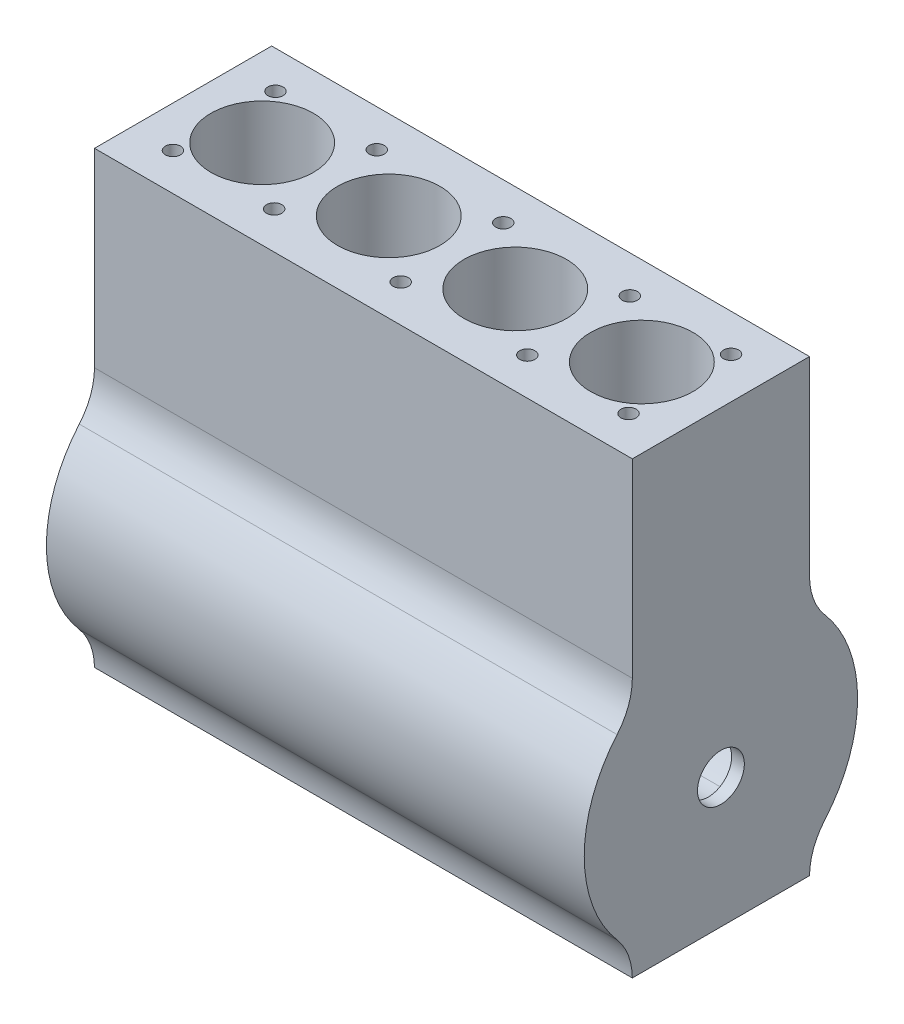
SolidWorks part; units mm, degrees
ref_plane "Front Plane" through (0, 0, 0) normal (0, 0, 1) x (1, 0, 0)
ref_plane "Top Plane" through (0, 0, 0) normal (0, 1, 0) x (1, 0, 0)
ref_plane "Right Plane" through (0, 0, 0) normal (1, 0, 0) x (0, 0, -1)
sketch "Sketch1" plane through (0, 0, 0) normal (0, 1, 0) x (1, 0, 0)
  line L0 (0, 0) -> (62.5, 0)
  line L1 (62.5, 0) -> (162.5, 0)
  line L2 (162.5, 0) -> (262.5, 0)
  line L3 (262.5, 0) -> (362.5, 0)
  line L4 (362.5, 0) -> (425, 0)
  line L5 (0, 0) -> (0, 70) construction
  line L6 (425, 0) -> (425, -70) construction
  line L8 (0, 70) -> (425, 70)
  line L9 (0, 70) -> (0, -70)
  line L10 (0, -70) -> (425, -70)
  line L11 (425, 70) -> (425, -70)
  circle A0 centre (62.5, 0) radius 40.5015
  circle A1 centre (162.5, 0) radius 40.5015
  circle A2 centre (262.5, 0) radius 40.5015
  circle A3 centre (362.5, 0) radius 40.5015
  dimension "D6" = 81.003
  dimension "D7" = 81.003
  dimension "D8" = 81.003
  dimension "D9" = 81.003
  dimension "D1" = 62.5
  dimension "D2" = 100
  dimension "D3" = 100
  dimension "D4" = 100
  dimension "D5" = 62.5
  dimension "D10" = 70
  dimension "D11" = 70
  dimension "D12" = 425
extrude "Boss-Extrude1" add sketch "Sketch1" along normal blind 350 contours A3 L3 A2 L2 A1 L1 A0 L0 L9 L10 L11 L4 | A3 L4 L11 L8 L9 L0 A0 L1 A1 L2 A2 L3 region at (212.5, 0, -44.4413) region at (212.5, 0, 44.4413)
sketch "Sketch2" plane through (0, 0, 0) normal (0, -1, 0) x (1, 0, 0)
  line L14 (415, -60) -> (415, 60)
  line L15 (10, -60) -> (415, -60)
  line L16 (10, 60) -> (10, -60)
  line L17 (415, 60) -> (10, 60)
  line L18 (415, -60) -> (415, 60)
  line L19 (10, -60) -> (415, -60)
  line L20 (10, 60) -> (10, -60)
  line L21 (415, 60) -> (10, 60)
  dimension "D1" = 10
extrude "Cut-Extrude1" cut sketch "Sketch2" against normal blind 250
sketch "Sketch3" plane through (0, 0, 0) normal (-1, 0, 0) x (0, 0, 1)
  circle A0 centre (0, 102.3197) radius 18.5
  dimension "D1" = 37
extrude "Cut-Extrude2" cut sketch "Sketch3" against normal blind 425
sketch "Sketch5" plane through (0, 0, 0) normal (-1, 0, 0) x (0, 0, 1)
  line L0 (-70, 184.5633) -> (-70, 20.0762)
  line L1 (-70, 350) -> (-70, 0) construction
  line L3 (70, 184.5633) -> (70, 20.0762)
  line L5 (70, 350) -> (70, 0) construction
  circle A0 centre (0, 102.3197) radius 108
  dimension "D1" = 216
extrude "Boss-Extrude4" add sketch "Sketch5" against normal blind 425 contours L1 A0 | A0 region at (0, 102.3197, -85.4554) region at (0, 102.3197, 85.4554)
ref_plane "Plane2" through (10, 0, 0) normal (-1, 0, 0) x (0, 0, 1)
sketch "Sketch7" plane through (10, 0, 0) normal (-1, 0, 0) x (0, 0, 1)
  circle A0 centre (0, 102.3197) radius 99
  dimension "D1" = 198
extrude "Cut-Extrude4" cut sketch "Sketch7" against normal blind 405
fillet "Fillet1" radius 20 4 edges at (212.5, 23.5733, -60) (212.5, 23.5733, 60) (212.5, 181.0661, -60) (212.5, 181.0661, 60)
fillet "Fillet2" radius 50 4 edges at (212.5, 20.0762, -70) (212.5, 20.0762, 70) (212.5, 184.5633, 70) (212.5, 184.5633, -70)
sketch "Sketch8" plane through (0, 350, 0) normal (0, 1, 0) x (1, 0, 0)
  line L0 (62.5, 40.5015) -> (362.5, 40.5015) construction
  line L1 (62.5, -40.5015) -> (362.5, -40.5015) construction
  line L2 (62.5, 0) -> (162.5, 0) construction
  line L3 (162.5, 0) -> (262.5, 0) construction
  line L4 (262.5, 0) -> (362.5, 0) construction
  line L5 (112.5, -40.5015) -> (112.5, 40.5015) construction
  line L6 (212.5, -40.5015) -> (212.5, 40.5015) construction
  line L7 (312.5, -40.5015) -> (312.5, 40.5015) construction
  line L8 (62.5, 40.5015) -> (12.5, 40.5015) construction
  line L9 (62.5, -40.5015) -> (12.5, -40.5015) construction
  line L10 (362.5, 40.5015) -> (412.5, 40.5015) construction
  line L11 (362.5, -40.5015) -> (412.5, -40.5015) construction
  line L12 (425, -82.0253) -> (425, -70) construction
  line L13 (0, 70) -> (425, 70)
  line L14 (0, 70) -> (0, -70)
  line L15 (0, -70) -> (425, -70)
  line L16 (425, 70) -> (425, -70)
  line L17 (0, -70) -> (425, -70) construction
  circle A0 centre (62.5, 0) radius 40.5015 construction
  circle A1 centre (362.5, 0) radius 40.5015 construction
  circle A2 centre (112.5, 40.5015) radius 6
  circle A3 centre (112.5, -40.5015) radius 6
  circle A4 centre (212.5, -40.5015) radius 6
  circle A5 centre (212.5, 40.5015) radius 6
  circle A6 centre (312.5, -40.5015) radius 6
  circle A7 centre (312.5, 40.5015) radius 6
  circle A8 centre (12.5, 40.5015) radius 6
  circle A9 centre (12.5, -40.5015) radius 6
  circle A10 centre (412.5, -40.5015) radius 6
  circle A11 centre (412.5, 40.5015) radius 6
  circle A12 centre (62.5, 0) radius 40.5015
  circle A13 centre (162.5, 0) radius 40.5015
  circle A14 centre (262.5, 0) radius 40.5015
  circle A15 centre (362.5, 0) radius 40.5015
  point P17 (112.5, 0)
  point P20 (212.5, 0)
  point P23 (312.5, 0)
  dimension "D4" = 12
  dimension "D5" = 12
  dimension "D6" = 12
  dimension "D7" = 12
  dimension "D8" = 12
  dimension "D9" = 12
  dimension "D14" = 12
  dimension "D15" = 12
  dimension "D16" = 12
  dimension "D17" = 12
  dimension "D1" = 100
  dimension "D2" = 100
  dimension "D3" = 100
  dimension "D10" = 50
  dimension "D11" = 50
  dimension "D12" = 50
  dimension "D13" = 50
extrude "Boss-Extrude5" add sketch "Sketch8" along normal blind 5.28
sketch "Sketch9" plane through (0, 355.28, 0) normal (0, 1, 0) x (1, 0, 0)
  line L0 (12.5, 40.5015) -> (0, 40.5015)
  line L1 (12.5, -40.5015) -> (0, -40.5015)
  line L2 (412.5, -40.5015) -> (425, -40.5015)
  line L3 (412.5, 40.5015) -> (425, 40.5015)
  line L4 (0, 70) -> (0, -70)
  line L5 (0, -70) -> (425, -70)
  line L6 (425, -70) -> (425, 70)
  line L7 (425, 70) -> (0, 70)
  line L8 (0, 70) -> (0, -70)
  line L9 (0, -70) -> (425, -70)
  line L10 (425, -70) -> (425, 70)
  line L11 (425, 70) -> (0, 70)
  line L12 (0, 40.5015) -> (32.5, 40.5015)
  line L13 (0, -40.5015) -> (32.5, -40.5015)
  line L14 (425, -40.5015) -> (392.5, -40.5015)
  line L15 (425, 40.5015) -> (392.5, 40.5015)
  circle A0 centre (32.5, 40.5015) radius 6
  circle A1 centre (32.5, -40.5015) radius 6
  circle A2 centre (392.5, -40.5015) radius 6
  circle A3 centre (392.5, 40.5015) radius 6
  circle A4 centre (112.5, 40.5015) radius 6
  circle A5 centre (112.5, -40.5015) radius 6
  circle A6 centre (212.5, -40.5015) radius 6
  circle A7 centre (212.5, 40.5015) radius 6
  circle A8 centre (312.5, 40.5015) radius 6
  circle A9 centre (312.5, -40.5015) radius 6
  circle M14 centre (312.5, -40.5015) radius 6
  circle M15 centre (212.5, -40.5015) radius 6
  circle M16 centre (112.5, 40.5015) radius 6
  circle M21 centre (112.5, -40.5015) radius 6
  circle M22 centre (212.5, 40.5015) radius 6
  circle M23 centre (312.5, 40.5015) radius 6
  dimension "D6" = 12
  dimension "D7" = 12
  dimension "D8" = 12
  dimension "D9" = 12
  dimension "D2" = 32.5
  dimension "D3" = 32.5
  dimension "D4" = 32.5
  dimension "D5" = 32.5
  dimension "D1" = 0
extrude "Cut-Extrude5" cut sketch "Sketch9" against normal blind 80 contours A0 | M16 | M22 | M15 | A1 | M21 | M14 | M23 | A3 | A2 region at (32.5, 355.28, 34.6712) region at (386.6697, 355.28, 40.5015) region at (386.6697, 355.28, -40.5015) region at (32.5, 355.28, -46.3318) region at (112.5, 355.28, -40.5015) region at (112.5, 355.28, 40.5015) region at (212.5, 355.28, 40.5015) region at (212.5, 355.28, -40.5015) region at (312.5, 355.28, -40.5015) region at (312.5, 355.28, 40.5015)
sketch "Sketch10" plane through (0, 355.28, 0) normal (0, 1, 0) x (1, 0, 0)
  circle A0 centre (12.5, 40.5015) radius 6
  circle A1 centre (12.5, -40.5015) radius 6
  circle A2 centre (412.5, -40.5015) radius 6
  circle A3 centre (412.5, 40.5015) radius 6
extrude "Boss-Extrude8" add sketch "Sketch10" against normal up to surface (5.28 mm away) up to face at (412.5, 350, 46.5015)
sketch "Sketch13" plane through (0, 250, 0) normal (0, -1, 0) x (1, 0, 0)
  line L0 (103.0015, 0) -> (121.9985, 0)
  line L1 (203.0015, 0) -> (221.9985, 0)
  line L2 (303.0015, 0) -> (321.9985, 0)
  line L3 (415, 60) -> (10, 60) construction
  line L4 (103.0015, -60) -> (121.9985, -60)
  line L5 (103.0015, -60) -> (103.0015, 60)
  line L6 (103.0015, 60) -> (121.9985, 60)
  line L7 (121.9985, -60) -> (121.9985, 60)
  line L8 (112.5, 60) -> (112.5, -60) construction
  line L9 (103.0015, 0) -> (121.9985, 0) construction
  line L11 (203.0015, -60) -> (221.9985, -60)
  line L12 (203.0015, -60) -> (203.0015, 60)
  line L13 (203.0015, 60) -> (221.9985, 60)
  line L14 (221.9985, -60) -> (221.9985, 60)
  line L15 (212.5, 60) -> (212.5, -60) construction
  line L16 (203.0015, 0) -> (221.9985, 0) construction
  line L17 (303.0015, -60) -> (321.9985, -60)
  line L18 (303.0015, -60) -> (303.0015, 60)
  line L19 (303.0015, 60) -> (321.9985, 60)
  line L20 (321.9985, -60) -> (321.9985, 60)
  line L21 (312.5, 60) -> (312.5, -60) construction
  line L22 (303.0015, 0) -> (321.9985, 0) construction
  circle A0 centre (62.5, 0) radius 40.5015 construction
  circle A1 centre (162.5, 0) radius 40.5015 construction
  circle A2 centre (262.5, 0) radius 40.5015 construction
  circle A3 centre (362.5, 0) radius 40.5015 construction
  point P17 (112.5, 0)
  point P23 (212.5, 0)
  point P27 (312.5, 0)
  line M17 (10, -60) -> (415, -60)
  line M19 (415, 60) -> (10, 60)
extrude "Boss-Extrude9" add sketch "Sketch13" along normal blind 147.68 contours L0 L7 L5 M19 | L1 L14 L12 M19 | L2 L20 L18 M19 | L7 L0 L5 M17 | L14 L1 L12 M17 | L20 L2 L18 M17 region at (112.5, 250, 30) region at (112.5, 250, -30) region at (212.5, 250, -30) region at (212.5, 250, 30) region at (312.5, 250, -30) region at (312.5, 250, 30)
sketch "Sketch14" plane through (103.0015, 0, 0) normal (-1, 0, 0) x (0, 0, 1)
  line L0 (-60, 102.32) -> (60, 102.32) construction
  circle A0 centre (0, 102.32) radius 20.5
  dimension "D1" = 41
extrude "Cut-Extrude6" cut sketch "Sketch14" against normal up to surface (218.997 mm away) up to face at (321.9985, 190.7818, 0)
sketch "Sketch15" plane through (0, 102.32, 0) normal (0, -1, 0) x (1, 0, 0)
  line L0 (103.0015, 20.5) -> (121.9985, -20.5) construction
  line L1 (121.9985, -20.5) -> (103.0015, -20.5) construction
  line L2 (103.0015, -20.5) -> (121.9985, 20.5) construction
  line L3 (121.9985, 0) -> (121.9985, 60) construction
  line L4 (103.0015, -40) -> (121.9985, -40)
  line L5 (103.0015, -40) -> (103.0015, 40)
  line L6 (103.0015, 40) -> (121.9985, 40)
  line L7 (121.9985, -40) -> (121.9985, 40)
  line L8 (112.5, 40) -> (112.5, -40) construction
  line L9 (103.0015, 0) -> (121.9985, 0) construction
  line L10 (103.0015, 20.5) -> (121.9985, 40) construction
  line L11 (121.9985, 20.5) -> (103.0015, 40) construction
  line L12 (103.0015, -20.5) -> (121.9985, -40) construction
  line L13 (103.0015, -40) -> (121.9985, -20.5) construction
  line L14 (203.0015, -40) -> (203.0015, 40)
  line L15 (203.0015, -40) -> (221.9985, -40)
  line L16 (221.9985, -40) -> (221.9985, 40)
  line L17 (203.0015, 40) -> (221.9985, 40)
  line L18 (303.0015, -40) -> (303.0015, 40)
  line L19 (303.0015, -40) -> (321.9985, -40)
  line L20 (321.9985, -40) -> (321.9985, 40)
  line L21 (303.0015, 40) -> (321.9985, 40)
  circle A0 centre (112.5, 30.25) radius 5
  circle A1 centre (112.5, -30.25) radius 5
  circle A2 centre (212.5, 30.25) radius 5
  circle A3 centre (212.5, -30.25) radius 5
  circle A4 centre (312.5, 30.25) radius 5
  circle A5 centre (312.5, -30.25) radius 5
  point P4 (112.5, 0)
  dimension "D2" = 10
  dimension "D3" = 10
  dimension "D1" = 80
  dimension "D4" = 3
extrude "Cut-Extrude7" cut sketch "Sketch15" against normal blind 50 contours A1 | A0 | A3 | A2 | A4 | A5 region at (112.5, 102.32, 30.25) region at (112.5, 102.32, -30.25) region at (212.5, 102.32, 30.25) region at (212.5, 102.32, -30.25) region at (312.5, 102.32, 30.25) region at (312.5, 102.32, -30.25)
sketch "Sketch16" plane through (0, 0, 60) normal (0, 0, 1) x (1, 0, 0)
  line L0 (221.9985, 190.4162) -> (203.0015, 190.4162)
  line L1 (203.0015, 190.4162) -> (203.0015, 102.32)
  line L2 (203.0015, 102.32) -> (221.9985, 102.32)
  line L3 (221.9985, 102.32) -> (221.9985, 190.4162)
  line L4 (121.9985, 190.4162) -> (103.0015, 190.4162)
  line L5 (103.0015, 190.4162) -> (103.0015, 102.32)
  line L6 (103.0015, 102.32) -> (121.9985, 102.32)
  line L7 (121.9985, 102.32) -> (121.9985, 190.4162)
  line L8 (121.9985, 190.4162) -> (103.0015, 190.4162)
  line L9 (103.0015, 190.4162) -> (103.0015, 102.32)
  line L10 (103.0015, 102.32) -> (121.9985, 102.32)
  line L11 (121.9985, 102.32) -> (121.9985, 190.4162)
  line L12 (321.9985, 190.4162) -> (303.0015, 190.4162)
  line L13 (303.0015, 190.4162) -> (303.0015, 102.32)
  line L14 (303.0015, 102.32) -> (321.9985, 102.32)
  line L15 (321.9985, 102.32) -> (321.9985, 190.4162)
  dimension "D1" = 0
  dimension "D2" = 3
extrude "Boss-Extrude10" add sketch "Sketch16" along normal up to surface (39 mm away) up to face at (212.5, 102.3197, 82.7773)
sketch "Sketch17" plane through (0, 0, -60) normal (0, 0, -1) x (-1, 0, 0)
  line L0 (-203.0015, 102.32) -> (-203.0015, 190.4162)
  line L1 (-203.0015, 190.4162) -> (-221.9985, 190.4162)
  line L2 (-221.9985, 190.4162) -> (-221.9985, 102.32)
  line L3 (-221.9985, 102.32) -> (-203.0015, 102.32)
  line L4 (-103.0015, 102.32) -> (-103.0015, 190.4162)
  line L5 (-103.0015, 190.4162) -> (-121.9985, 190.4162)
  line L6 (-121.9985, 190.4162) -> (-121.9985, 102.32)
  line L7 (-121.9985, 102.32) -> (-103.0015, 102.32)
  line L8 (-103.0015, 102.32) -> (-103.0015, 190.4162)
  line L9 (-103.0015, 190.4162) -> (-121.9985, 190.4162)
  line L10 (-121.9985, 190.4162) -> (-121.9985, 102.32)
  line L11 (-121.9985, 102.32) -> (-103.0015, 102.32)
  line L12 (-303.0015, 102.32) -> (-303.0015, 190.4162)
  line L13 (-303.0015, 190.4162) -> (-321.9985, 190.4162)
  line L14 (-321.9985, 190.4162) -> (-321.9985, 102.32)
  line L15 (-321.9985, 102.32) -> (-303.0015, 102.32)
  dimension "D1" = 0
  dimension "D2" = 3
extrude "Boss-Extrude11" add sketch "Sketch17" along normal blind 78
sketch "Sketch18" plane through (425, 0, 0) normal (1, 0, 0) x (0, 0, -1)
  line L0 (127.5949, 211.6062) -> (70, 211.6062)
  line L1 (127.5926, -6.9694) -> (70, 0)
  line L4 (-70, 0) -> (70, 0)
  line L5 (70, 205.101) -> (70, 355.28)
  line L6 (70, 355.28) -> (-70, 355.28)
  line L7 (-70, 355.28) -> (-70, 205.101)
  line L8 (-70, 0) -> (70, 0)
  line L9 (70, 205.101) -> (70, 355.28)
  line L10 (70, 355.28) -> (-70, 355.28)
  line L11 (-70, 355.28) -> (-70, 205.101)
  arc A0 (127.5926, -6.9694) -> (127.5949, 211.6062) centre (0, 102.3197) ccw
  arc A6 (82.0238, 32.0624) -> (70, 0) centre (119.9978, -0.4641) ccw
  arc A7 (82.0238, 32.0624) -> (82.0253, 172.5753) centre (0, 102.3197) ccw
  arc A8 (70, 205.101) -> (82.0253, 172.5753) centre (120, 205.101) ccw
  arc A9 (-82.0253, 172.5753) -> (-70, 205.101) centre (-120, 205.101) ccw
  arc A10 (-82.0253, 172.5753) -> (-82.0238, 32.0624) centre (0, 102.3197) ccw
  arc A11 (-70, 0) -> (-82.0238, 32.0624) centre (-119.9978, -0.4641) ccw
  arc A12 (82.0238, 32.0624) -> (70, 0) centre (119.9978, -0.4641) ccw
  arc A13 (82.0238, 32.0624) -> (82.0253, 172.5753) centre (0, 102.3197) ccw
  arc A14 (70, 205.101) -> (82.0253, 172.5753) centre (120, 205.101) ccw
  arc A15 (-82.0253, 172.5753) -> (-70, 205.101) centre (-120, 205.101) ccw
  arc A16 (-82.0253, 172.5753) -> (-82.0238, 32.0624) centre (0, 102.3197) ccw
  arc A17 (-70, 0) -> (-82.0238, 32.0624) centre (-119.9978, -0.4641) ccw
  arc M13 (70, 0) -> (82.0238, 32.0624) centre (119.9978, -0.4641) cw
  arc M14 (82.0238, 32.0624) -> (82.0253, 172.5753) centre (0, 102.3197) ccw
  arc M15 (82.0253, 172.5753) -> (70, 205.101) centre (120, 205.101) cw
  line M16 (70, 205.101) -> (70, 355.28)
  dimension "D1" = 0
  dimension "D2" = 60
extrude "Cut-Extrude8" cut sketch "Sketch18" against normal up to surface (425 mm away) contours L1 A0 L0 M16 M15 M14 M13 region at (425, 103.8518, -122.7429) up to face at (0, 102.3197, 18.5)
sketch "Sketch19" plane through (0, 0, 0) normal (0, -1, 0) x (1, 0, 0)
  line L0 (0, 60) -> (10, 70) construction
  line L1 (10, 60) -> (0, 60) construction
  line L2 (10, 60) -> (10, 70) construction
  line L3 (10, 70) -> (0, 70) construction
  line L4 (0, 60) -> (0, 70) construction
  line L5 (10, 60) -> (0, 70) construction
  line L6 (0, 0) -> (425, 0) construction
  line L7 (425, -70) -> (425, 70) construction
  circle A0 centre (5, 65) radius 2
  circle A1 centre (88, 65) radius 2
  circle A2 centre (171, 65) radius 2
  circle A3 centre (254, 65) radius 2
  circle A4 centre (337, 65) radius 2
  circle A5 centre (420, 65) radius 2
  circle A6 centre (420, -65) radius 2
  circle A7 centre (337, -65) radius 2
  circle A8 centre (254, -65) radius 2
  circle A9 centre (171, -65) radius 2
  circle A10 centre (88, -65) radius 2
  circle A11 centre (5, -65) radius 2
  dimension "D1" = 4
  dimension "D2" = 6
extrude "Cut-Extrude9" cut sketch "Sketch19" against normal blind 17
